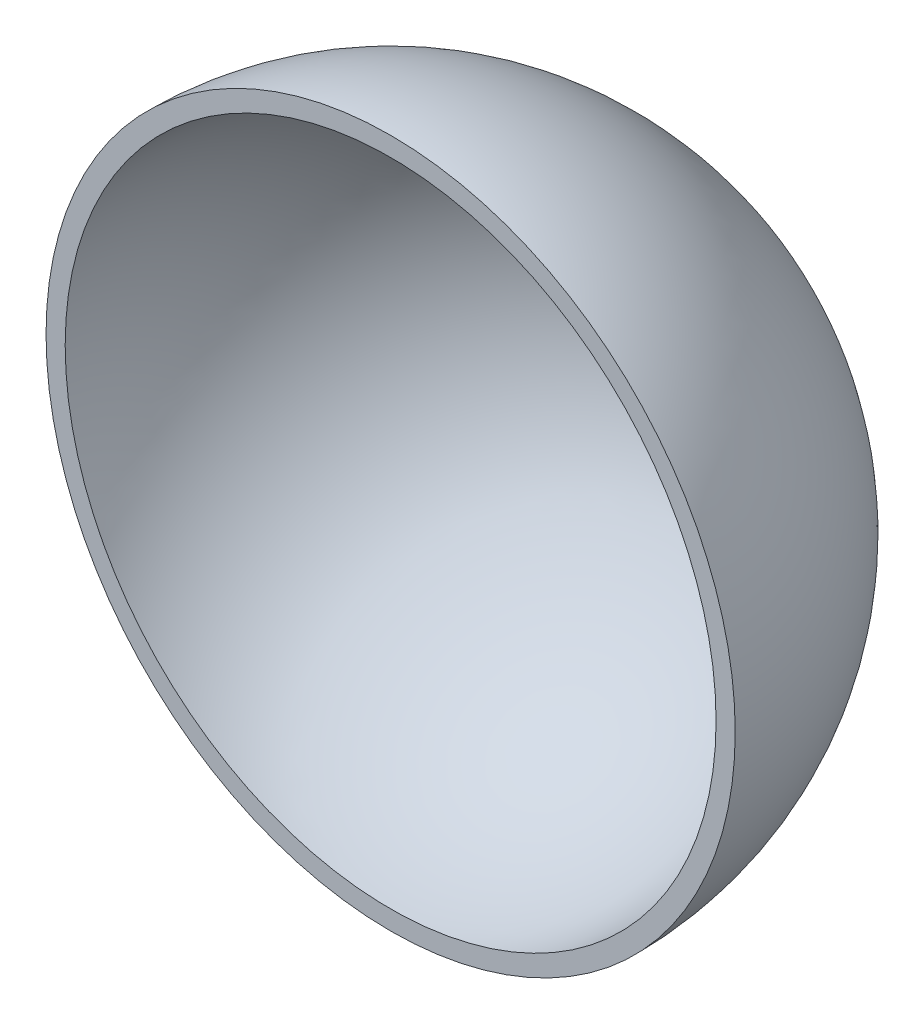
SolidWorks part; units mm, degrees
ref_plane "Front Plane" through (0, 0, 0) normal (0, 0, 1) x (1, 0, 0)
ref_plane "Top Plane" through (0, 0, 0) normal (0, 1, 0) x (1, 0, 0)
ref_plane "Right Plane" through (0, 0, 0) normal (1, 0, 0) x (0, 0, -1)
sketch "Sketch1" plane through (0, 0, 0) normal (0, 0, 1) x (1, 0, 0)
  line L0 (0, 0) -> (0, 180)
  line L1 (0, 175) -> (-3.2791, 175) construction
  line L2 (0, 5) -> (-3.6918, 5) construction
  arc A0 (0, 180) -> (0, 0) centre (0, 90) cw
  arc A1 (0, 175) -> (0, 5) centre (0, 90) cw
  circle A2 centre (0, 90) radius 2.5
  dimension "D4" = 5
  dimension "D1" = 180
  dimension "D2" = 5
  dimension "D3" = 5
revolve "Revolve1" add sketch "Sketch1" angle 180 about L0 region at (2.0125, 2.5, 0)
extrude "Cut-Extrude1" cut sketch "Sketch1<3>" against normal up to surface (89.9653 mm away) contours L0 A2 | L0 A2 region at (-1.061, 90, 0) region at (1.061, 90, 0) up to face at (-90, 90, 0)
sketch "Sketch1<3>" plane through (0, 0, 0) normal (0, 0, 1) x (1, 0, 0) same geometry as "Sketch1"
